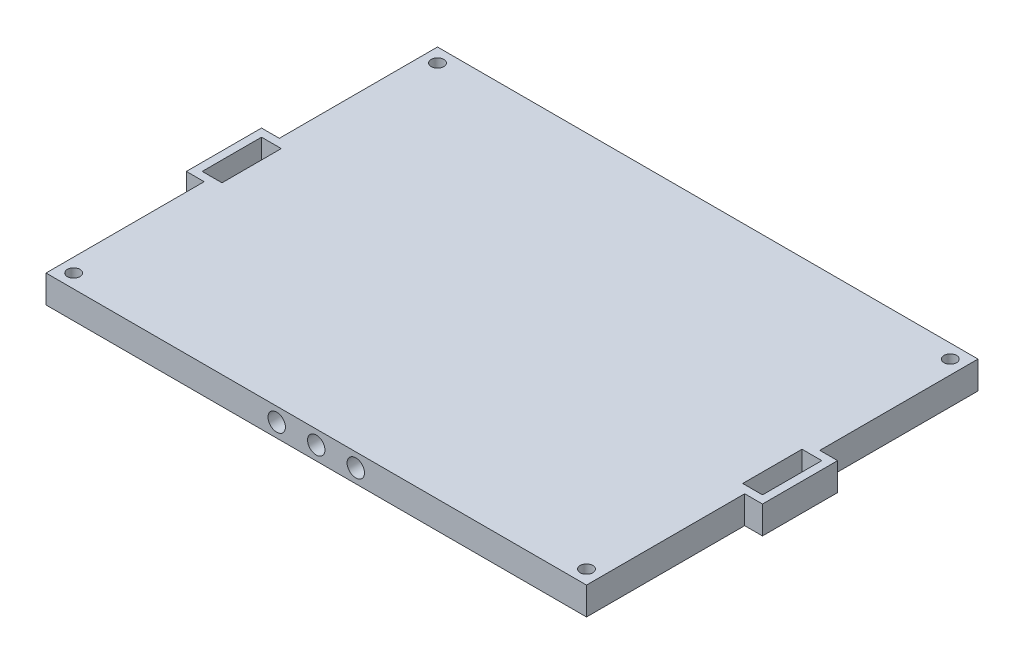
SolidWorks part; units mm, degrees
ref_plane "Front Plane" through (0, 0, 0) normal (0, 0, 1) x (1, 0, 0)
ref_plane "Top Plane" through (0, 0, 0) normal (0, 1, 0) x (1, 0, 0)
ref_plane "Right Plane" through (0, 0, 0) normal (1, 0, 0) x (0, 0, -1)
sketch "Sketch1" plane through (0, 0, 0) normal (0, 1, 0) x (1, 0, 0)
  line L0 (-68.342, -49.5) -> (-68.342, 49.5)
  line L1 (-61.342, -42.5) -> (61.342, -42.5)
  line L2 (-61.342, -42.5) -> (-61.342, 42.5)
  line L3 (-61.342, 42.5) -> (61.342, 42.5)
  line L4 (61.342, -42.5) -> (61.342, 42.5)
  line L5 (-61.342, -42.5) -> (61.342, 42.5) construction
  line L6 (-61.342, 42.5) -> (61.342, -42.5) construction
  line L7 (-68.342, 49.5) -> (68.342, 49.5)
  line L8 (68.342, -49.5) -> (68.342, 49.5)
  line L9 (-68.342, -49.5) -> (68.342, -49.5)
  line L10 (-68.342, 0) -> (-65.842, 0) construction
  line L11 (-65.842, 0) -> (-65.842, 7.5) construction
  line L12 (0, 0) -> (0, 42.5) construction
  line L13 (-70.842, -7.5) -> (-65.842, -7.5)
  line L14 (-70.842, -7.5) -> (-70.842, 7.5)
  line L15 (-70.842, 7.5) -> (-65.842, 7.5)
  line L16 (-65.842, -7.5) -> (-65.842, 7.5)
  line L17 (-70.842, -7.5) -> (-65.842, 7.5) construction
  line L18 (-70.842, 7.5) -> (-65.842, -7.5) construction
  line L19 (-72.842, -9.5) -> (-72.842, 9.5)
  line L20 (-72.842, 9.5) -> (-63.842, 9.5)
  line L21 (-63.842, -9.5) -> (-63.842, 9.5)
  line L22 (-72.842, -9.5) -> (-63.842, -9.5)
  line L23 (72.842, -9.5) -> (63.842, -9.5)
  line L24 (63.842, -9.5) -> (63.842, 9.5)
  line L25 (72.842, 9.5) -> (63.842, 9.5)
  line L26 (72.842, -9.5) -> (72.842, 9.5)
  line L27 (70.842, 7.5) -> (65.842, 7.5)
  line L28 (65.842, -7.5) -> (65.842, 7.5)
  line L29 (70.842, -7.5) -> (65.842, -7.5)
  line L30 (70.842, -7.5) -> (70.842, 7.5)
  point P0 (0, 0)
  dimension "D2" = 2
  dimension "D1" = 7
extrude "Boss-Extrude1" add sketch "Sketch1" along normal blind 7 contours L25 L8 L7 L0 L20 L21 L22 L9 L23 L24 L4 L1 L2 L3 | L8 L29 L28 L27 L25 L24 L23 | L30 L29 L8 L23 L26 L25 L27 | L19 L22 L0 L13 L14 L15 L20 | L0 L22 L21 L20 L15 L16 L13 | L2 L1 L4 L3 region at (-66.6543, 0, 29.5) region at (-71.3733, 0, 0) region at (-65.3108, 0, 0) region at (65.3108, 0, 0) region at (71.3733, 0, 0)
sketch "Sketch3" plane through (0, 0, 0) normal (0, 1, 0) x (1, 0, 0)
  line L0 (0, 0) -> (13.5974, 0) construction
  line L1 (0, 0) -> (0, -8.9797) construction
  line L2 (64.8156, -49.5) -> (64.8156, -46) construction
  line L3 (-68.342, -49.5) -> (68.342, -49.5) construction
  line L4 (68.342, -46) -> (64.842, -46) construction
  line L5 (68.342, -49.5) -> (68.342, -9.5) construction
  line L6 (0, 0) -> (0, 37.5) construction
  line L7 (0, 37.5) -> (-37.5, 37.5) construction
  circle A0 centre (64.842, -46) radius 1.6
  circle A1 centre (64.842, 46) radius 1.6
  circle A2 centre (-64.842, 46) radius 1.6
  circle A3 centre (-64.842, -46) radius 1.6
  circle A4 centre (-37.5, 37.5) radius 2.2
  circle A5 centre (37.5, 37.5) radius 2.2
  circle A6 centre (37.5, -37.5) radius 2.2
  circle A7 centre (-37.5, -37.5) radius 2.2
extrude "Cut-Extrude3" cut sketch "Sketch3" along normal up to next contours A2 | A3 | A0 | A1 region at (64.842, 0, 46) region at (64.842, 0, -46) region at (-64.842, 0, -46) region at (-64.842, 0, 46)
extrude "Cut-Extrude4" cut sketch "Sketch3<4>" along normal blind 4 contours A4 | A5 | A6 | A7 region at (-37.5, 0, -37.5) region at (37.5, 0, -37.5) region at (37.5, 0, 37.5) region at (-37.5, 0, 37.5)
sketch "Sketch3<4>" plane through (0, 0, 0) normal (0, 1, 0) x (1, 0, 0) same geometry as "Sketch3"
sketch "Sketch4" plane through (0, 0, 49.5) normal (0, 0, 1) x (1, 0, 0)
  line L0 (0, 0) -> (0, 3.5) construction
  line L1 (-68.342, 0) -> (68.342, 0) construction
  line L2 (0, 3.5) -> (10, 3.5) construction
  circle A0 centre (0, 3.5) radius 2.2
  circle A1 centre (10, 3.5) radius 2.2
  circle A2 centre (-10, 3.5) radius 2.2
extrude "Cut-Extrude5" cut sketch "Sketch4" against normal blind 4
